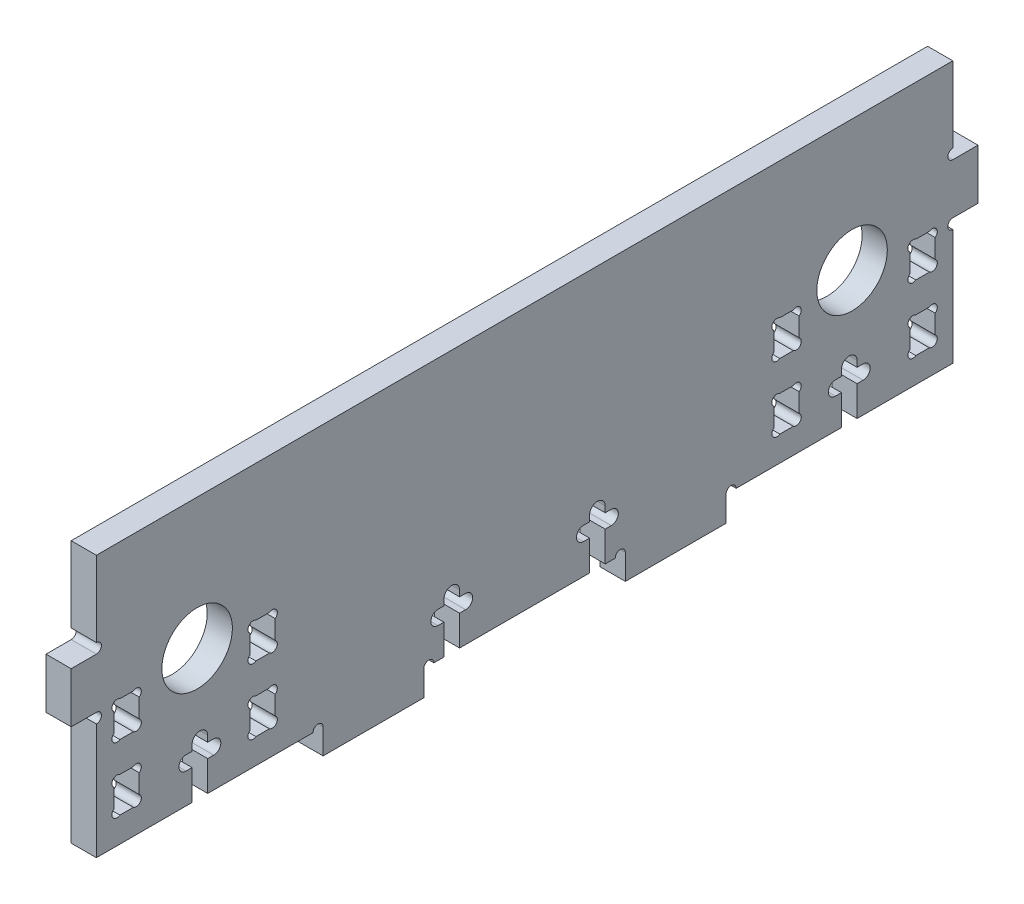
SolidWorks part; units mm, degrees
ref_plane "정면" through (0, 0, 0) normal (0, 0, 1) x (1, 0, 0)
ref_plane "윗면" through (0, 0, 0) normal (0, 1, 0) x (1, 0, 0)
ref_plane "우측면" through (0, 0, 0) normal (1, 0, 0) x (0, 0, -1)
sketch "스케치1" plane through (0, 0, 0) normal (1, 0, 0) x (0, 0, -1)
  line L1 (0, 0) -> (170, 0)
  line L2 (0, 0) -> (0, 52)
  line L3 (0, 52) -> (170, 52)
  line L4 (170, 0) -> (170, 52)
  dimension "D1" = 170
  dimension "D2" = 52
extrude "보스-돌출1" add sketch "스케치1" along normal blind 5
sketch "스케치2" plane through (5, 0, 0) normal (1, 0, 0) x (0, 0, -1)
  line L0 (170, 26) -> (150, 26) construction
  line L1 (170, 0) -> (170, 52) construction
  line L2 (150, 26) -> (20, 26) construction
  line L3 (20, 26) -> (0, 26) construction
  line L4 (0, 52) -> (0, 0) construction
  circle A0 centre (150, 26) radius 7
  circle A1 centre (20, 26) radius 7
  dimension "D2" = 14
  dimension "D1" = 20
extrude "컷-돌출1" cut sketch "스케치2" against normal blind 10
sketch "스케치3" plane through (5, 0, 0) normal (1, 0, 0) x (0, 0, -1)
  line L0 (0, 0) -> (170, 0) construction
  line L1 (45, 0) -> (65, 0)
  line L2 (45, 0) -> (45, -5)
  line L3 (45, -5) -> (65, -5)
  line L4 (65, 0) -> (65, -5)
  line L5 (0, -5) -> (45, -5) construction
  line L6 (65, -5) -> (105, -5) construction
  line L7 (125, 0) -> (105, 0)
  line L8 (125, 0) -> (125, -5)
  line L9 (125, -5) -> (105, -5)
  line L10 (105, 0) -> (105, -5)
  line L11 (125, -5) -> (170, -5) construction
  line L12 (170, -5) -> (170, 0) construction
  line L13 (0, 0) -> (0, -5) construction
  line L14 (0, 0) -> (0, -5) construction
  line L15 (0, -5) -> (45, -5) construction
  dimension "D1" = 45
  dimension "D2" = 20
extrude "보스-돌출2" add sketch "스케치3" against normal blind 5
sketch "스케치6" plane through (5, 0, 0) normal (1, 0, 0) x (0, 0, -1)
  line L0 (151, 0) -> (151, 6)
  line L1 (147.9, 10) -> (151, 10) construction
  line L2 (146.7, 6) -> (146.7, 8.8) construction
  line L3 (151, 6) -> (151, 8.8) construction
  line L4 (147.9, 0) -> (151, 0)
  line L5 (146.7, 8.8) -> (147.9, 8.8)
  line L6 (147.9, 0) -> (147.9, 6)
  line L7 (152.2, 8.8) -> (152.2, 6) construction
  line L8 (147.9, 6) -> (146.7, 6)
  line L9 (147.9, 8.8) -> (147.9, 6) construction
  line L10 (151, 8.8) -> (151, 10)
  line L11 (147.9, 6) -> (151, 6) construction
  line L12 (147.9, 8.8) -> (151, 8.8) construction
  line L13 (151, 8.8) -> (152.2, 8.8)
  line L14 (147.9, 8.8) -> (147.9, 10)
  line L15 (149.45, 10) -> (149.45, 12.1831) construction
  line L16 (152.2, 6) -> (151, 6)
  line L18 (65, 0) -> (105, 0) construction
  line L19 (101, 0) -> (101, 6)
  line L20 (97.9, 10) -> (101, 10) construction
  line L21 (96.7, 6) -> (96.7, 8.8) construction
  line L22 (101, 6) -> (101, 8.8) construction
  line L23 (97.9, 0) -> (101, 0)
  line L24 (96.7, 8.8) -> (97.9, 8.8)
  line L25 (97.9, 0) -> (97.9, 6)
  line L26 (102.2, 8.8) -> (102.2, 6) construction
  line L27 (97.9, 6) -> (96.7, 6)
  line L28 (97.9, 8.8) -> (97.9, 6) construction
  line L29 (101, 8.8) -> (101, 10)
  line L30 (97.9, 6) -> (101, 6) construction
  line L31 (97.9, 8.8) -> (101, 8.8) construction
  line L32 (101, 8.8) -> (102.2, 8.8)
  line L33 (97.9, 8.8) -> (97.9, 10)
  line L34 (99.45, 10) -> (99.45, 12.1831) construction
  line L35 (102.2, 6) -> (101, 6)
  line L37 (105, 0) -> (105, -5) construction
  line L71 (85, 52) -> (85, 0) construction
  line L72 (170, 52) -> (0, 52) construction
  line L89 (70.55, 10) -> (70.55, 12.1831) construction
  line L90 (72.1, 8.8) -> (69, 8.8) construction
  line L91 (72.1, 6) -> (69, 6) construction
  line L92 (72.1, 8.8) -> (72.1, 6) construction
  line L93 (67.8, 8.8) -> (67.8, 6) construction
  line L94 (69, 6) -> (69, 8.8) construction
  line L95 (73.3, 6) -> (73.3, 8.8) construction
  line L96 (72.1, 10) -> (69, 10) construction
  line L97 (20.55, 10) -> (20.55, 12.1831) construction
  line L98 (22.1, 8.8) -> (19, 8.8) construction
  line L99 (22.1, 6) -> (19, 6) construction
  line L100 (22.1, 8.8) -> (22.1, 6) construction
  line L101 (17.8, 8.8) -> (17.8, 6) construction
  line L102 (19, 6) -> (19, 8.8) construction
  line L103 (23.3, 6) -> (23.3, 8.8) construction
  line L104 (22.1, 10) -> (19, 10) construction
  line L123 (67.8, 6) -> (69, 6)
  line L124 (72.1, 8.8) -> (72.1, 10)
  line L125 (69, 8.8) -> (67.8, 8.8)
  line L126 (69, 8.8) -> (69, 10)
  line L127 (72.1, 6) -> (73.3, 6)
  line L128 (72.1, 0) -> (72.1, 6)
  line L129 (73.3, 8.8) -> (72.1, 8.8)
  line L130 (72.1, 0) -> (69, 0)
  line L131 (69, 0) -> (69, 6)
  line L132 (17.8, 6) -> (19, 6)
  line L133 (22.1, 8.8) -> (22.1, 10)
  line L134 (19, 8.8) -> (17.8, 8.8)
  line L135 (19, 8.8) -> (19, 10)
  line L136 (22.1, 6) -> (23.3, 6)
  line L137 (22.1, 0) -> (22.1, 6)
  line L138 (23.3, 8.8) -> (22.1, 8.8)
  line L139 (22.1, 0) -> (19, 0)
  line L140 (19, 0) -> (19, 6)
  arc A0 (151, 10) -> (147.9, 10) centre (149.45, 10) ccw
  arc A1 (146.7, 8.8) -> (146.7, 6) centre (146.7, 7.4) ccw
  arc A2 (152.2, 6) -> (152.2, 8.8) centre (152.2, 7.4) ccw
  arc A3 (101, 10) -> (97.9, 10) centre (99.45, 10) ccw
  arc A4 (96.7, 8.8) -> (96.7, 6) centre (96.7, 7.4) ccw
  arc A5 (102.2, 6) -> (102.2, 8.8) centre (102.2, 7.4) ccw
  arc A18 (67.8, 6) -> (67.8, 8.8) centre (67.8, 7.4) cw
  arc A19 (73.3, 8.8) -> (73.3, 6) centre (73.3, 7.4) cw
  arc A20 (69, 10) -> (72.1, 10) centre (70.55, 10) cw
  arc A21 (17.8, 6) -> (17.8, 8.8) centre (17.8, 7.4) cw
  arc A22 (23.3, 8.8) -> (23.3, 6) centre (23.3, 7.4) cw
  arc A23 (19, 10) -> (22.1, 10) centre (20.55, 10) cw
  dimension "D1" = 3.1
  dimension "D2" = 4
  dimension "D3" = 5.5
  dimension "D4" = 2.8
  dimension "D7" = 3.1
  dimension "D9" = 5.5
  dimension "D10" = 2.8
  dimension "D12" = 50
extrude "컷-돌출2" cut sketch "스케치6" against normal blind 10
sketch "스케치8" plane through (5, 0, 0) normal (1, 0, 0) x (0, 0, -1)
  line L0 (170, 0) -> (170, 52) construction
  line L1 (170, 35) -> (175, 35)
  line L2 (170, 35) -> (170, 25)
  line L3 (170, 25) -> (175, 25)
  line L4 (175, 35) -> (175, 25)
  line L5 (175, 25) -> (175, -5) construction
  line L8 (85, 0) -> (85, 52) construction
  line L9 (72.1, 0) -> (97.9, 0) construction
  line L10 (170, 52) -> (0, 52) construction
  line L11 (-5, 35) -> (-5, 25)
  line L12 (0, 25) -> (-5, 25)
  line L13 (0, 35) -> (0, 25)
  line L14 (0, 35) -> (-5, 35)
  line L15 (151, 0) -> (170, 0) construction
  dimension "D1" = 25
  dimension "D2" = 10
extrude "보스-돌출3" add sketch "스케치8" against normal blind 5
sketch "스케치7" plane through (5, 0, 0) normal (1, 0, 0) x (0, 0, -1)
  line L0 (65, 0) -> (69, 0) construction
  line L1 (22.1, 0) -> (45, 0) construction
  line L2 (101, 0) -> (105, 0) construction
  line L3 (125, 0) -> (147.9, 0) construction
  line L4 (170, 35) -> (170, 52) construction
  line L5 (170, 0) -> (170, 25) construction
  line L6 (0, 52) -> (0, 35) construction
  line L7 (0, 25) -> (0, 0) construction
  circle A0 centre (66, 0) radius 1
  circle A1 centre (44, 0) radius 1
  circle A2 centre (104, 0) radius 1
  circle A3 centre (126, 0) radius 1
  circle A4 centre (170, 36) radius 1
  circle A5 centre (170, 24) radius 1
  circle A6 centre (0, 36) radius 1
  circle A7 centre (0, 24) radius 1
  dimension "D1" = 2
extrude "컷-돌출3" cut sketch "스케치7" against normal blind 10
sketch "스케치10" plane through (0, 0, 0) normal (-1, 0, 0) x (0, 0, 1)
  line L0 (-166.5, 25) -> (-161.5, 18) construction
  line L1 (-166.5, 18) -> (-161.5, 18)
  line L2 (-166.5, 18) -> (-166.5, 25)
  line L3 (-166.5, 25) -> (-161.5, 25)
  line L4 (-161.5, 18) -> (-161.5, 25)
  line L5 (-161.5, 25) -> (-166.5, 18) construction
  line L6 (-85, 52) -> (-85, 0) construction
  line L7 (-139.5, 18) -> (-134.5, 18)
  line L8 (-139.5, 18) -> (-139.5, 25)
  line L9 (-139.5, 25) -> (-134.5, 25)
  line L10 (-134.5, 18) -> (-134.5, 25)
  line L11 (-166.5, 5) -> (-161.5, 5)
  line L12 (-166.5, 5) -> (-166.5, 12)
  line L13 (-166.5, 12) -> (-161.5, 12)
  line L14 (-161.5, 5) -> (-161.5, 12)
  line L15 (-139.5, 12) -> (-134.5, 12)
  line L16 (-139.5, 12) -> (-139.5, 5)
  line L17 (-139.5, 5) -> (-134.5, 5)
  line L18 (-134.5, 12) -> (-134.5, 5)
  line L19 (-170, 52) -> (0, 52) construction
  line L20 (-72.1, 0) -> (-97.9, 0) construction
  line L21 (-8.5, 25) -> (-3.5, 18) construction
  line L22 (-3.5, 25) -> (-8.5, 18) construction
  line L23 (-35.5, 12) -> (-35.5, 5)
  line L24 (-30.5, 5) -> (-35.5, 5)
  line L25 (-30.5, 12) -> (-30.5, 5)
  line L26 (-30.5, 12) -> (-35.5, 12)
  line L27 (-8.5, 5) -> (-8.5, 12)
  line L28 (-3.5, 12) -> (-8.5, 12)
  line L29 (-3.5, 5) -> (-3.5, 12)
  line L30 (-3.5, 5) -> (-8.5, 5)
  line L31 (-35.5, 18) -> (-35.5, 25)
  line L32 (-30.5, 25) -> (-35.5, 25)
  line L33 (-30.5, 18) -> (-30.5, 25)
  line L34 (-30.5, 18) -> (-35.5, 18)
  line L35 (-8.5, 18) -> (-8.5, 25)
  line L36 (-3.5, 25) -> (-8.5, 25)
  line L37 (-3.5, 18) -> (-3.5, 25)
  line L38 (-3.5, 18) -> (-8.5, 18)
extrude "컷-돌출4" cut sketch "스케치10" against normal blind 10
sketch "스케치11" plane through (5, 0, 0) normal (1, 0, 0) x (0, 0, -1)
  line L0 (85, 52) -> (85, 0) construction
  line L1 (170, 52) -> (0, 52) construction
  line L2 (72.1, 0) -> (97.9, 0) construction
  line L3 (161.5, 25) -> (166.5, 18) construction
  line L4 (166.5, 25) -> (161.5, 18) construction
  line L5 (139.5, 18) -> (161.5, 18) construction
  line L6 (161.5, 18) -> (161.5, 12) construction
  line L7 (161.5, 12) -> (139.5, 12) construction
  line L8 (139.5, 12) -> (139.5, 18) construction
  line L9 (150.5, 18) -> (150.5, 12) construction
  line L10 (139.5, 15) -> (161.5, 15) construction
  line L11 (134.5, 25) -> (139.5, 18) construction
  line L12 (139.5, 25) -> (134.5, 18) construction
  line L13 (139.5, 5) -> (134.5, 12) construction
  line L14 (134.5, 5) -> (139.5, 12) construction
  line L15 (166.5, 5) -> (161.5, 12) construction
  line L16 (161.5, 5) -> (166.5, 12) construction
  line L17 (8.5, 5) -> (3.5, 12) construction
  line L18 (3.5, 5) -> (8.5, 12) construction
  line L19 (35.5, 5) -> (30.5, 12) construction
  line L20 (30.5, 5) -> (35.5, 12) construction
  line L21 (30.5, 25) -> (35.5, 18) construction
  line L22 (35.5, 25) -> (30.5, 18) construction
  line L23 (30.5, 15) -> (8.5, 15) construction
  line L24 (19.5, 18) -> (19.5, 12) construction
  line L25 (30.5, 12) -> (30.5, 18) construction
  line L26 (8.5, 12) -> (30.5, 12) construction
  line L27 (8.5, 18) -> (8.5, 12) construction
  line L28 (30.5, 18) -> (8.5, 18) construction
  line L29 (3.5, 25) -> (8.5, 18) construction
  line L30 (8.5, 25) -> (3.5, 18) construction
  circle A0 centre (165.9188, 24.1863) radius 1
  circle A1 centre (162.0812, 24.1863) radius 1
  circle A2 centre (165.9188, 18.8137) radius 1
  circle A3 centre (162.0812, 18.8137) radius 1
  circle A4 centre (138.9188, 18.8137) radius 1
  circle A5 centre (135.0812, 18.8137) radius 1
  circle A6 centre (138.9188, 24.1863) radius 1
  circle A7 centre (135.0812, 24.1863) radius 1
  circle A8 centre (135.0812, 5.8137) radius 1
  circle A9 centre (138.9188, 5.8137) radius 1
  circle A10 centre (135.0812, 11.1863) radius 1
  circle A11 centre (138.9188, 11.1863) radius 1
  circle A12 centre (162.0812, 11.1863) radius 1
  circle A13 centre (165.9188, 11.1863) radius 1
  circle A14 centre (162.0812, 5.8137) radius 1
  circle A15 centre (165.9188, 5.8137) radius 1
  circle A16 centre (4.0812, 5.8137) radius 1
  circle A17 centre (7.9188, 5.8137) radius 1
  circle A18 centre (4.0812, 11.1863) radius 1
  circle A19 centre (7.9188, 11.1863) radius 1
  circle A20 centre (31.0812, 11.1863) radius 1
  circle A21 centre (34.9188, 11.1863) radius 1
  circle A22 centre (31.0812, 5.8137) radius 1
  circle A23 centre (34.9188, 5.8137) radius 1
  circle A24 centre (34.9188, 24.1863) radius 1
  circle A25 centre (31.0812, 24.1863) radius 1
  circle A26 centre (34.9188, 18.8137) radius 1
  circle A27 centre (31.0812, 18.8137) radius 1
  circle A28 centre (7.9188, 18.8137) radius 1
  circle A29 centre (4.0812, 18.8137) radius 1
  circle A30 centre (7.9188, 24.1863) radius 1
  circle A31 centre (4.0812, 24.1863) radius 1
  dimension "D1" = 2
extrude "컷-돌출5" cut sketch "스케치11" against normal blind 10
